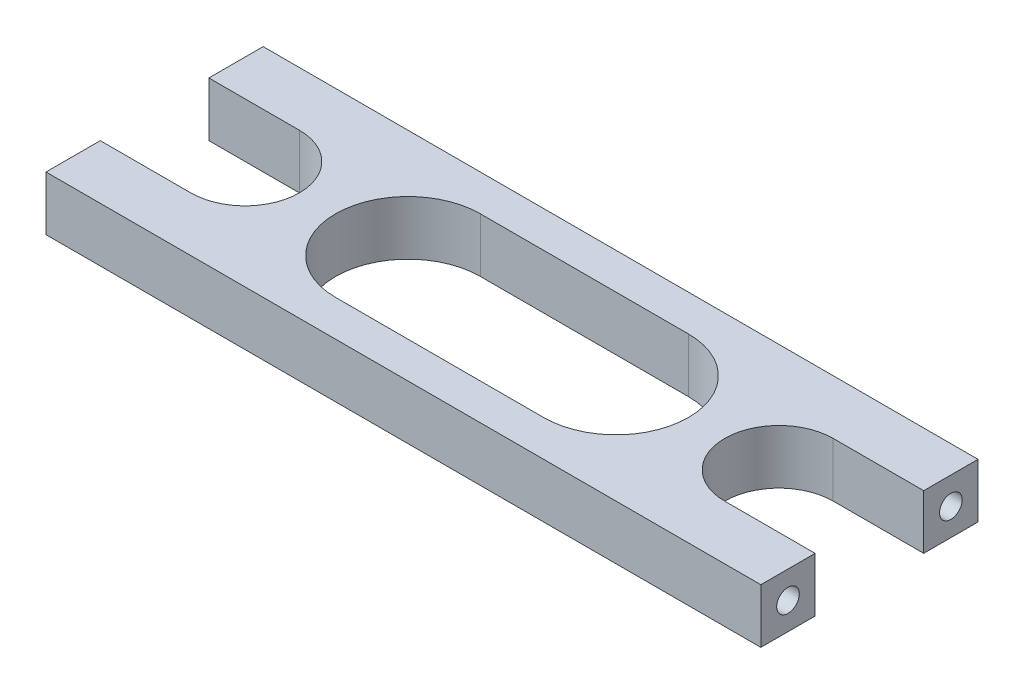
SolidWorks part; units mm, degrees
material "1060 Alloy"
ref_plane "Front Plane" through (0, 0, 0) normal (0, 0, 1) x (1, 0, 0)
ref_plane "Top Plane" through (0, 0, 0) normal (0, 1, 0) x (1, 0, 0)
ref_plane "Right Plane" through (0, 0, 0) normal (1, 0, 0) x (0, 0, -1)
sketch "Sketch1" plane through (0, 0, 0) normal (0, 1, 0) x (1, 0, 0)
  line L1 (0, 0) -> (79, 0)
  line L2 (0, 0) -> (0, 24)
  line L3 (0, 24) -> (79, 24)
  line L4 (79, 0) -> (79, 24)
  dimension "D1" = 24
  dimension "D2" = 79
extrude "Boss-Extrude1" add sketch "Sketch1" along normal blind 6
sketch "Sketch2" plane through (0, 6, 0) normal (0, 1, 0) x (1, 0, 0)
  line L0 (0, 12) -> (10, 12) construction
  line L1 (0, 24) -> (0, 0) construction
  line L2 (0, 18) -> (10, 18)
  line L3 (0, 6) -> (10, 6)
  line L4 (79, 12) -> (69, 12) construction
  line L5 (79, 0) -> (79, 24) construction
  line L6 (79, 6) -> (69, 6)
  line L7 (79, 18) -> (69, 18)
  line L8 (28, 12) -> (51, 12) construction
  line L9 (28, 20) -> (51, 20)
  line L10 (28, 4) -> (51, 4)
  arc A0 (0, 18) -> (0, 6) centre (0, 12) ccw
  arc A1 (10, 6) -> (10, 18) centre (10, 12) ccw
  arc A2 (79, 6) -> (79, 18) centre (79, 12) ccw
  arc A3 (69, 18) -> (69, 6) centre (69, 12) ccw
  arc A4 (28, 20) -> (28, 4) centre (28, 12) ccw
  arc A5 (51, 4) -> (51, 20) centre (51, 12) ccw
  point P4 (5, 12)
  point P9 (74, 12)
  point P18 (39.5, 12)
  dimension "D4" = 6
  dimension "D5" = 8
  dimension "D1" = 10
  dimension "D2" = 18
  dimension "D3" = 18
extrude "Cut-Extrude1" cut sketch "Sketch2" against normal up to next
hole_wizard "Tap Drill for M3 Tap1" positions "Sketch4" profile "Sketch3" hole size "M3" standard "ISO"
sketch "Sketch4" plane through (0, 0, 0) normal (-1, 0, 0) x (0, 0, 1)
  line L0 (-24, 0) -> (-18, 0) construction
  line L1 (-24, 6) -> (-24, 0) construction
  line L2 (0, 6) -> (0, 0) construction
  point P0 (-21, 3)
  point P2 (-3, 3)
  dimension "D1" = 3
  dimension "D2" = 3
  dimension "D3" = 3
sketch "Sketch3" plane through (0, 3, -21) normal (0, 1, 0) x (0, 0, 1)
  line L0 (0, 0) -> (0, 10.7511)
  line L1 (0, 10.7511) -> (1.25, 10)
  line L2 (1.25, 10) -> (1.25, 0)
  line L5 (1.25, 0) -> (0, 0)
  line L10 (0, 10.7511) -> (-1.25, 10) construction
  line L11 (0, -6.35) -> (0, 107.95) construction
  dimension "Hole Dia." = 2.5
  dimension "Hole Depth" = 10
  dimension "Drill Angle" = 118
hole_wizard "Tap Drill for M3 Tap2" positions "Sketch6" profile "Sketch5" hole size "M3" standard "ISO"
sketch "Sketch6" plane through (79, 0, 0) normal (1, 0, 0) x (0, 0, -1)
  line L0 (0, 0) -> (6, 0) construction
  line L1 (0, 6) -> (0, 0) construction
  line L2 (24, 6) -> (24, 0) construction
  point P0 (3, 3)
  point P2 (21, 3)
  dimension "D1" = 3
  dimension "D2" = 3
  dimension "D3" = 3
sketch "Sketch5" plane through (79, 3, -3) normal (0, 1, 0) x (0, 0, -1)
  line L0 (0, 0) -> (0, 10.7511)
  line L1 (0, 10.7511) -> (1.25, 10)
  line L2 (1.25, 10) -> (1.25, 0)
  line L5 (1.25, 0) -> (0, 0)
  line L10 (0, 10.7511) -> (-1.25, 10) construction
  line L11 (0, -6.35) -> (0, 107.95) construction
  dimension "Hole Dia." = 2.5
  dimension "Hole Depth" = 10
  dimension "Drill Angle" = 118
